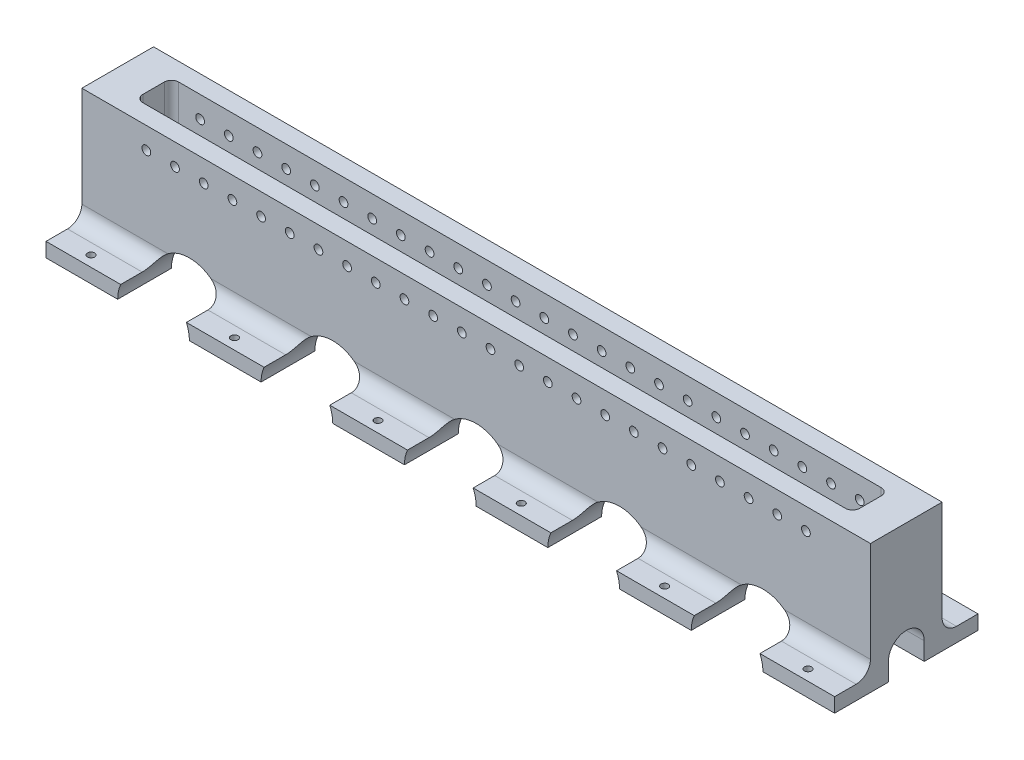
SolidWorks part; units mm, degrees
ref_plane "Front Plane" through (0, 0, 0) normal (0, 0, 1) x (1, 0, 0)
ref_plane "Top Plane" through (0, 0, 0) normal (0, 1, 0) x (1, 0, 0)
ref_plane "Right Plane" through (0, 0, 0) normal (1, 0, 0) x (0, 0, -1)
sketch "Sketch1" plane through (0, 0, 0) normal (0, 1, 0) x (1, 0, 0)
  line L1 (-50, -2.5) -> (50, -2.5)
  line L2 (-50, -2.5) -> (-50, 2.5)
  line L3 (-50, 2.5) -> (50, 2.5)
  line L4 (50, -2.5) -> (50, 2.5)
  line L5 (-50, -2.5) -> (50, 2.5) construction
  line L6 (-50, 2.5) -> (50, -2.5) construction
  line L7 (-55, -5) -> (55, -5)
  line L8 (-55, -5) -> (-55, 5)
  line L9 (-55, 5) -> (55, 5)
  line L10 (55, -5) -> (55, 5)
  line L11 (-55, -5) -> (55, 5) construction
  line L12 (-55, 5) -> (55, -5) construction
  point P0 (0, 0)
  point P6 (0, 0)
  dimension "D1" = 5
  dimension "D2" = 10
  dimension "D3" = 100
  dimension "D4" = 110
extrude "Boss-Extrude1" add sketch "Sketch1" along normal blind 18
sketch "Sketch2" plane through (55, 0, 0) normal (1, 0, 0) x (0, 0, -1)
  line L0 (0, 0) -> (0, 18) construction
  line L1 (-5, 0) -> (5, 0) construction
  line L3 (0, 0) -> (0, 18) construction
  line L4 (-5, 18) -> (5, 18) construction
  line L6 (-2.5, 0) -> (2.5, 0)
  line L7 (-2.5, 0) -> (-2.5, 5)
  line L8 (-2.5, 5) -> (2.5, 5)
  line L9 (2.5, 0) -> (2.5, 5)
  dimension "D1" = 5
  dimension "D2" = 5
extrude "Cut-Extrude1" cut sketch "Sketch2" against normal through all
fillet "Fillet1" radius 2.5 4 edges at (52.5, 5, 2.5) (52.5, 5, -2.5) (-52.5, 5, -2.5) (-52.5, 5, 2.5) tangent propagation no
sketch "Sketch3" plane through (0, 0, 5) normal (0, 0, 1) x (1, 0, 0)
  line L0 (-55, 15) -> (55, 15) construction
  line L1 (-55, 18) -> (-55, 0) construction
  line L2 (55, 18) -> (55, 0) construction
  line L3 (-55, 18) -> (55, 18) construction
  line L4 (-50, 15) -> (-50, 18) construction
  circle A0 centre (-46, 15) radius 0.61
  dimension "D2" = 1.22
  dimension "D3" = 4
  dimension "D1" = 3
extrude "Cut-Extrude2" cut sketch "Sketch3" against normal through all
pattern_linear "LPattern1" count 24 spacing 4 along (1, 0, 0) of "Cut-Extrude2"
sketch "Sketch6" plane through (0, 0, 0) normal (0, -1, 0) x (1, 0, 0)
  line L0 (-55, -5) -> (-55, -2.5) construction
  line L1 (55, -5) -> (-55, -5)
  line L2 (55, -5) -> (55, -10)
  line L3 (55, -10) -> (-55, -10)
  line L4 (-55, -5) -> (-55, -10)
  line L5 (55, 5) -> (55, 2.5) construction
  line L6 (55, 5) -> (-55, 5)
  line L7 (55, 5) -> (55, 10)
  line L8 (55, 10) -> (-55, 10)
  line L9 (-55, 5) -> (-55, 10)
  line L10 (-55, 2.5) -> (-55, 5) construction
  line L11 (-55, 5) -> (55, 5) construction
  dimension "D1" = 5
  dimension "D2" = 5
extrude "Boss-Extrude2" add sketch "Sketch6" against normal blind 2
fillet "Fillet2" radius 2 2 edges
sketch "Sketch5" plane through (0, 0, 5) normal (0, 0, 1) x (1, 0, 0)
  line L0 (-55, 0) -> (55, 0) construction
  line L1 (-50, 0) -> (-50, 18) construction
  line L2 (-55, 18) -> (55, 18) construction
  line L3 (-45, 0) -> (-35, 0)
  arc A0 (-45, 0) -> (-35, 0) centre (-40, 0) cw
  dimension "D1" = 5
  dimension "D2" = 10
extrude "Cut-Extrude4" cut sketch "Sketch5" against normal through all both and the other way through all
pattern_linear "LPattern2" count 5 spacing 20 along (1, 0, 0) of "Cut-Extrude4"
sketch "Sketch7" plane through (0, 2, 0) normal (0, 1, 0) x (1, 0, 0)
  line L0 (49.7913, 10) -> (49.7913, 8.5) construction
  line L1 (44.5826, 10) -> (55, 10) construction
  line L2 (49.7913, 8.5) -> (44.5826, 8.5) construction
  line L3 (44.5826, 7) -> (44.5826, 10) construction
  line L4 (49.7913, -10) -> (49.7913, -8.5) construction
  line L5 (55, -10) -> (44.5826, -10) construction
  line L6 (44.5826, -8.5) -> (49.7913, -8.5) construction
  line L7 (44.5826, -7) -> (44.5826, -10) construction
  circle A0 centre (49.7913, 8.5) radius 0.5
  circle A1 centre (49.7913, -8.5) radius 0.5
  dimension "D1" = 1
extrude "Cut-Extrude5" cut sketch "Sketch7" against normal blind 2
pattern_linear "LPattern3" count 24 spacing 20 along (-1, 0, 0) of "Cut-Extrude5"
fillet "Fillet3" radius 1 4 edges at (-50, 10.25, 2.5) (-50, 10.25, -2.5) (50, 10.25, -2.5) (50, 10.25, 2.5)
ref_plane "Plane1" through (30, 0, 0) normal (-1, 0, 0) x (0, 0, 1)
sketch "Sketch9" plane through (30, 0, 0) normal (-1, 0, 0) x (0, 0, 1)
  line L0 (-2.5, 5.5) -> (2.5, 5.5) construction
  line L1 (-2.5, 2.5) -> (-2.5, 18) construction
  line L2 (2.5, 5.5) -> (2.5, 3)
  line L3 (2.5, 18) -> (2.5, 2.5) construction
  line L4 (-2.5, 0) -> (2.5, 0)
  line L5 (-2.5, 5) -> (-2.5, 0)
  line L6 (2.5, 5) -> (-2.5, 5)
  line L7 (2.5, 0) -> (2.5, 5)
  line L8 (-2.5, 0) -> (2.5, 0) construction
  line L9 (-2.5, 5) -> (-2.5, 0) construction
  line L10 (2.5, 5) -> (-2.5, 5) construction
  line L11 (2.5, 0) -> (2.5, 5) construction
  line L12 (0, 0) -> (0, 15.9626) construction
  line L13 (-2.5, 5.5) -> (-2.5, 3)
  line L15 (-2.5, 5.5) -> (-2.5, 8.5)
  line L16 (-2.5, 8.5) -> (0, 8.5)
  line L17 (0, 8.5) -> (2.5, 8.5)
  line L18 (2.5, 8.5) -> (2.5, 5.5)
  arc A0 (-2.5, 3) -> (0, 5.5) centre (0, 3) cw
  arc A1 (2.5, 3) -> (0, 5.5) centre (0, 3) ccw
  dimension "D2" = 3
  dimension "D3" = 2.5
  dimension "D4" = 3
  dimension "D1" = 0
extrude "Boss-Extrude3" add sketch "Sketch9" along normal blind 1 and the other way blind 1
pattern_linear "LPattern4" count 4 spacing 20 along (-1, 0, 0) of "Boss-Extrude3"
